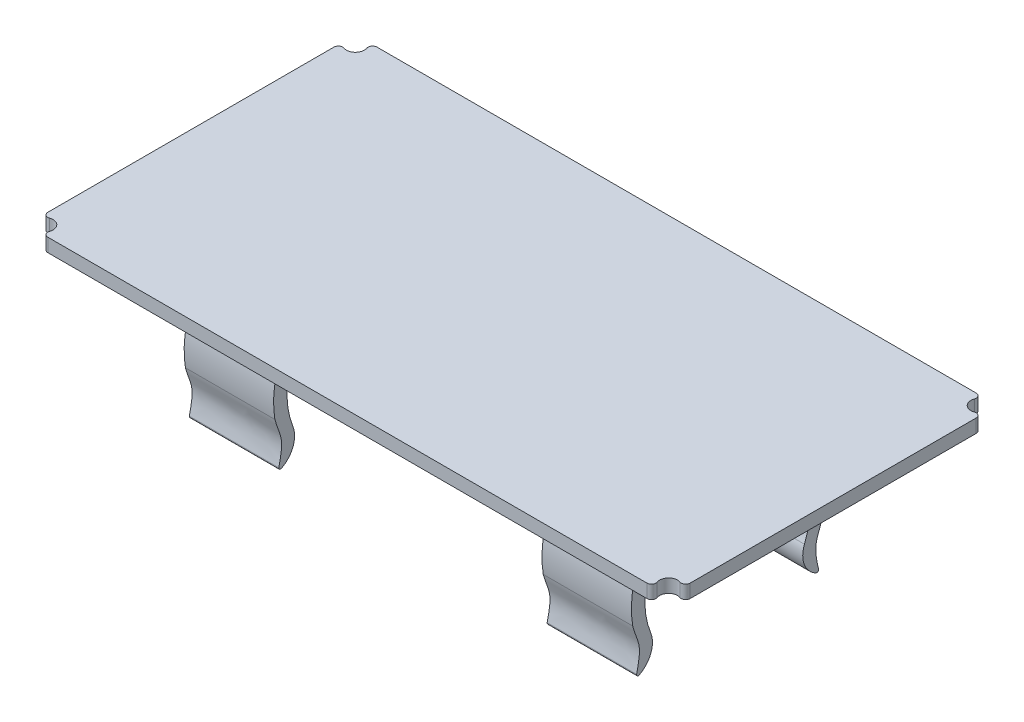
SolidWorks part; units mm, degrees
ref_plane "Front Plane" through (0, 0, 0) normal (0, 0, 1) x (1, 0, 0)
ref_plane "Top Plane" through (0, 0, 0) normal (0, 1, 0) x (1, 0, 0)
ref_plane "Right Plane" through (0, 0, 0) normal (1, 0, 0) x (0, 0, -1)
sketch "Sketch1" plane through (0, 0, 0) normal (0, 1, 0) x (1, 0, 0)
  line L1 (2.4142, 0) -> (69.3858, 0)
  line L2 (0, 2.4142) -> (0, 34.3858)
  line L3 (2.4142, 36.8) -> (69.3858, 36.8)
  line L4 (71.8, 2.4142) -> (71.8, 34.3858)
  arc A0 (0.6667, 34.8572) -> (1.9428, 36.1333) centre (1, 35.8) ccw
  arc A1 (1.9428, 0.6667) -> (0.6667, 1.9428) centre (1, 1) ccw
  arc A2 (71.1333, 1.9428) -> (69.8572, 0.6667) centre (70.8, 1) ccw
  arc A3 (69.8572, 36.1333) -> (71.1333, 34.8572) centre (70.8, 35.8) ccw
  arc A4 (69.8572, 36.1333) -> (69.3858, 36.8) centre (69.3858, 36.3) ccw
  arc A5 (71.8, 34.3858) -> (71.1333, 34.8572) centre (71.3, 34.3858) ccw
  arc A6 (71.1333, 1.9428) -> (71.8, 2.4142) centre (71.3, 2.4142) ccw
  arc A7 (69.8572, 0.6667) -> (69.3858, 0) centre (69.3858, 0.5) cw
  arc A8 (2.4142, 0) -> (1.9428, 0.6667) centre (2.4142, 0.5) cw
  arc A9 (0, 2.4142) -> (0.6667, 1.9428) centre (0.5, 2.4142) ccw
  arc A10 (2.4142, 36.8) -> (1.9428, 36.1333) centre (2.4142, 36.3) ccw
  arc A11 (0, 34.3858) -> (0.6667, 34.8572) centre (0.5, 34.3858) cw
  dimension "D3" = 1
  dimension "D7" = 1
  dimension "D2" = 0.5
  dimension "D4" = 1
  dimension "D5" = 1
  dimension "D6" = 1
  dimension "D8" = 1
  dimension "D9" = 1
  dimension "D10" = 1
extrude "Boss-Extrude1" add sketch "Sketch1" along normal blind 1.5
sketch "Sketch2" plane through (0, 0, 0) normal (0, -1, 0) x (1, 0, 0)
  line L0 (0, -18.4) -> (71.8, -18.4) construction
  line L1 (0, -34.3858) -> (0, -2.4142) construction
  line L2 (71.8, -2.4142) -> (71.8, -34.3858) construction
  line L3 (3, -12.6466) -> (68, -12.6466) construction
  dimension "D1" = 65
  dimension "D2" = 3
sketch "Sketch3" plane through (0, 0, 0) normal (-1, 0, 0) x (0, 0, 1)
  line L0 (-36.8, 1.5) -> (-36.8, 0) construction
  line L1 (-23.4312, 0) -> (-13.3688, 0)
  line L2 (-18.4, 0) -> (-18.4, -19) construction
  line L3 (-34.3858, 0) -> (-2.4142, 0) construction
  line L4 (-28.2815, -16.3501) -> (-8.5185, -16.3501) construction
  arc A0 (-23.4312, 0) -> (-29.0074, -11.2452) centre (-18.4, -9.5) ccw
  arc A1 (-9.8083, -12.9272) -> (-26.9917, -12.9272) centre (-18.4, -9.5) ccw
  arc A2 (-28.5695, -16.1394) -> (-28.2815, -16.3501) centre (-28.3721, -16.1718) ccw
  circle A3 centre (-18.4, -9.5) radius 10.75 construction
  arc A4 (-28.2815, -16.3501) -> (-26.9917, -12.9272) centre (-29.5113, -13.9322) ccw
  arc A5 (-8.2305, -16.1394) -> (-8.5185, -16.3501) centre (-8.4279, -16.1718) cw
  arc A6 (-8.5185, -16.3501) -> (-9.8083, -12.9272) centre (-7.2887, -13.9322) cw
  arc A8 (-7.7926, -11.2452) -> (-13.3688, 0) centre (-18.4, -9.5) ccw
  circle A10 centre (-18.4, -9.5) radius 9.25 construction
  spline S0 degree 3 poles (-29.0074, -11.2452) (-28.9168, -11.6449) (-28.6294, -12.3512) (-28.0702, -14.044) (-28.3784, -15.2421) (-28.5695, -16.1394) knots 0 0 0 0 0.314196 0.453998 1 1 1 1
  spline S1 degree 3 poles (-7.7926, -11.2452) (-7.8832, -11.6449) (-8.1706, -12.3512) (-8.7298, -14.044) (-8.4216, -15.2421) (-8.2305, -16.1394) knots 0 0 0 0 0.314196 0.453998 1 1 1 1
  point P2 (-36.8, 0.75)
  point P5 (-18.4, -9.5)
  point P6 (-33.8544, -1.1798)
  point P7 (-32.928, 0)
  point P12 (-25.4426, -5.8774)
  point P13 (-7.4, -9.5)
  point P15 (-7.4, -9.5)
  point P20 (-26.369, -7.0572)
  point P23 (-9.3151, -6.7225)
  point P29 (-9.3151, -6.7225)
  line M1 (-34.3858, 0) -> (-2.4142, 0)
  dimension "D1" = 18.4
  dimension "D4" = 0.2
  dimension "D5" = 5.0312
  dimension "D6" = 18.5
  dimension "D7" = 5.0312
  dimension "D2" = 9.5
  dimension "D3" = 1.5
extrude "Boss-Extrude2" add sketch "Sketch3" against normal blind 10 from offset 10 contours M1 region at (0, -0.027, -18.4) offset against normal yes
extrude "Boss-Extrude3" add sketch "Sketch3<3>" against normal blind 10 from offset 50 offset against normal yes
sketch "Sketch3<3>" plane through (0, 0, 0) normal (-1, 0, 0) x (0, 0, 1) same geometry as "Sketch3"
fillet "Fillet1" radius 2 4 edges at (55, 0, -23.4312) (15, 0, -23.4312) (55, 0, -13.3688) (15, 0, -13.3688)
